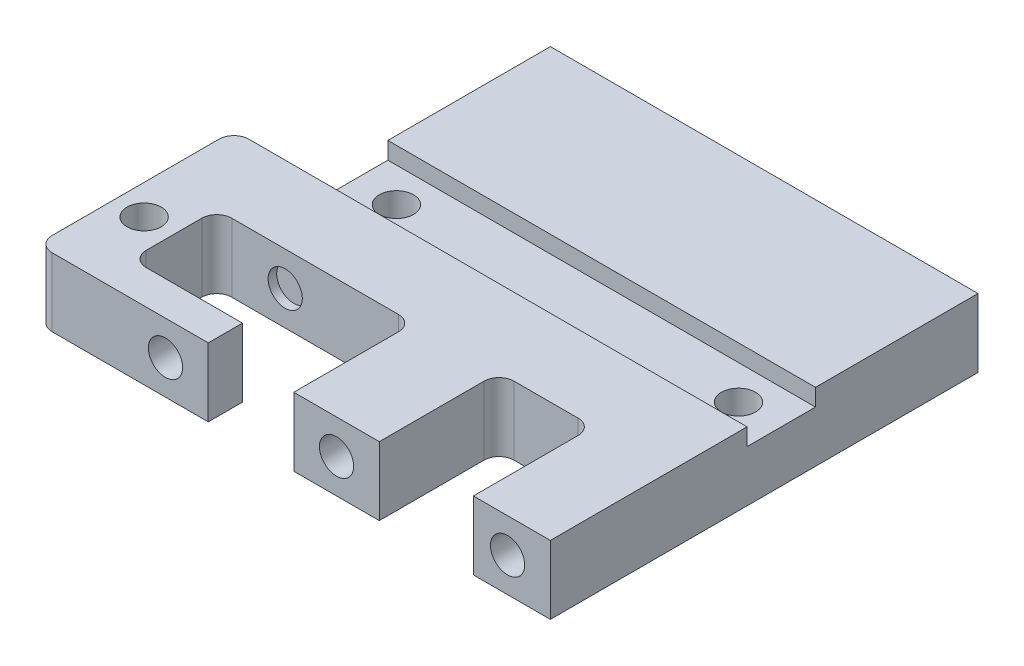
SolidWorks part; units mm, degrees
material "PVC rigide"
ref_plane "Plan de face" through (0, 0, 0) normal (0, 0, 1) x (1, 0, 0)
ref_plane "Plan de dessus" through (0, 0, 0) normal (0, 1, 0) x (1, 0, 0)
ref_plane "Plan de droite" through (0, 0, 0) normal (1, 0, 0) x (0, 0, -1)
sketch "Esquisse1" plane through (0, 0, 0) normal (0, 1, 0) x (1, 0, 0)
  line L1 (-57.1481, 46.0417) -> (-7.1481, 46.0417)
  line L2 (-57.1481, 46.0417) -> (-57.1481, 10.0417)
  line L4 (-7.1481, 46.0417) -> (-7.1481, 16.0417)
  line L5 (-48.1481, 10.0417) -> (-37.1481, 10.0417)
  line L6 (-16.1481, 10.0417) -> (-16.1481, -3.9583)
  line L7 (-16.1481, -3.9583) -> (-7.1481, -3.9583)
  line L8 (-7.1481, -3.9583) -> (-7.1481, 16.0417)
  line L9 (-27.1481, 10.0417) -> (-16.1481, 10.0417)
  line L10 (-48.1481, 10.0417) -> (-57.1481, 10.0417)
  line L11 (-37.1481, 10.0417) -> (-37.1481, -3.9583)
  line L12 (-37.1481, -3.9583) -> (-27.1481, -3.9583)
  line L13 (-27.1481, 10.0417) -> (-27.1481, -3.9583)
  dimension "D4" = 20
  dimension "D1" = 50
  dimension "D2" = 14
  dimension "D3" = 50
  dimension "D5" = 9
  dimension "D6" = 20
extrude "Boss.-Extru.1" add sketch "Esquisse1" along normal blind 8
sketch "Esquisse3" plane through (0, 0, -46.0417) normal (0, 0, -1) x (-1, 0, 0)
  line L0 (7.1481, 4) -> (57.1481, 4) construction
  line L1 (7.1481, 8) -> (7.1481, 0) construction
  line L2 (57.1481, 8) -> (57.1481, 0) construction
  circle A0 centre (12.1481, 4) radius 2
  circle A1 centre (52.1481, 4) radius 2
  dimension "D1" = 4
  dimension "D2" = 5
  dimension "D3" = 5
extrude "Enlèv. mat.-Extru.2" cut sketch "Esquisse3" against normal blind 10
sketch "Esquisse4" plane through (0, 8, 0) normal (0, 1, 0) x (1, 0, 0)
  line L0 (-62.8741, 23.0417) -> (2.0024, 23.0417) construction
  line L1 (-7.1481, 46.0417) -> (-57.1481, 46.0417) construction
  line L2 (-57.1481, 46.0417) -> (-57.1481, 10.0417) construction
  line L3 (-7.1481, -3.9583) -> (-7.1481, 46.0417) construction
  circle A0 centre (-52.1481, 23.0417) radius 2
  circle A1 centre (-12.1481, 23.0417) radius 2
  dimension "D2" = 4
  dimension "D1" = 23
  dimension "D3" = 5
  dimension "D4" = 5
extrude "Enlèv. mat.-Extru.3" cut sketch "Esquisse4" against normal blind 10
chamfer "Chanfrein1" distance 2.5 angle 45 2 edges at (-52.1481, 0, -25.0417) (-12.1481, 0, -25.0417)
sketch "Esquisse5" plane through (0, 8, 0) normal (0, 1, 0) x (1, 0, 0)
  line L0 (-57.1481, 46.0417) -> (-57.1481, 10.0417) construction
  line L1 (-57.1481, 27.0417) -> (-7.1481, 27.0417)
  line L2 (-57.1481, 27.0417) -> (-57.1481, 19.0417)
  line L3 (-57.1481, 19.0417) -> (-7.1481, 19.0417)
  line L4 (-7.1481, 27.0417) -> (-7.1481, 19.0417)
  line L5 (-7.1481, -3.9583) -> (-7.1481, 46.0417) construction
  circle A0 centre (-52.1481, 23.0417) radius 2 construction
  dimension "D1" = 4
  dimension "D2" = 8
extrude "Enlèv. mat.-Extru.4" cut sketch "Esquisse5" against normal blind 2
sketch "Esquisse6" plane through (-57.1481, 0, 0) normal (-1, 0, 0) x (0, 0, 1)
  line L0 (-46.0417, 0) -> (-10.0417, 0) construction
  line L1 (-19.0417, 8) -> (3.9583, 8)
  line L2 (-19.0417, 8) -> (-19.0417, 0)
  line L3 (-19.0417, 0) -> (3.9583, 0)
  line L4 (3.9583, 8) -> (3.9583, 0)
  line L9 (3.9583, 8) -> (3.9583, 0) construction
extrude "Boss.-Extru.2" add sketch "Esquisse6" along normal blind 10
sketch "Esquisse7" plane through (-57.1481, 0, 0) normal (1, 0, 0) x (0, 0, -1)
  line L0 (10.0417, 0) -> (-3.9583, 0) construction
  line L1 (-3.9583, 8) -> (0.0417, 8)
  line L2 (-3.9583, 8) -> (-3.9583, 0)
  line L3 (-3.9583, 0) -> (0.0417, 0)
  line L4 (0.0417, 8) -> (0.0417, 0)
  dimension "D1" = 4
extrude "Boss.-Extru.3" add sketch "Esquisse7" along normal blind 10
sketch "Esquisse8" plane through (0, 8, 0) normal (0, 1, 0) x (1, 0, 0)
  line L0 (-60.1481, 8.2917) -> (-60.1481, 1.7917)
  line L1 (-57.1481, 10.0417) -> (-37.1481, 10.0417) construction
  line L2 (-47.1481, 0.0417) -> (-57.1481, 0.0417) construction
  line L3 (-67.1481, -3.9583) -> (-67.1481, 19.0417) construction
  line L4 (-58.3981, 10.0417) -> (-54.6427, 10.0417)
  line L5 (-54.6427, 10.0417) -> (-54.6427, 0.0417)
  line L6 (-54.6427, 0.0417) -> (-58.3981, 0.0417)
  arc A0 (-58.3981, 10.0417) -> (-60.1481, 8.2917) centre (-58.3981, 8.2917) ccw
  arc A1 (-60.1481, 1.7917) -> (-58.3981, 0.0417) centre (-58.3981, 1.7917) ccw
  point P11 (-60.1481, 5.0417)
  dimension "D1" = 3.5
  dimension "D2" = 7
extrude "Enlèv. mat.-Extru.5" cut sketch "Esquisse8" against normal up to next
sketch "Esquisse2" plane through (0, 0, 3.9583) normal (0, 0, 1) x (1, 0, 0)
  line L2 (-7.1481, 8) -> (-7.1481, 0) construction
  circle A0 centre (-52.1481, 4) radius 2
  circle A1 centre (-12.1481, 4) radius 2
  circle A2 centre (-32.1481, 4) radius 2
  point P15 (-12.1481, 4)
  dimension "D1" = 4
  dimension "D3" = 5
extrude "Enlèv. mat.-Extru.1" cut sketch "Esquisse2" against normal blind 15
fillet "Congé1" radius 1.75 6 edges at (-16.1481, 4, -10.0417) (-27.1481, 4, -10.0417) (-37.1481, 4, -10.0417) (-57.1481, 3, -19.0417) (-67.1481, 4, 3.9583) (-67.1481, 4, -19.0417)
sketch "Esquisse10" plane through (0, 8, 0) normal (0, 1, 0) x (1, 0, 0)
  line L0 (-60.1481, 5.0417) -> (-67.1481, 5.0417) construction
  line L1 (-60.1481, 8.2917) -> (-60.1481, 1.7917) construction
  line L2 (-67.1481, -2.2083) -> (-67.1481, 17.2917) construction
  circle A0 centre (-63.6481, 5.0417) radius 2
  dimension "D1" = 4
extrude "Enlèv. mat.-Extru.7" cut sketch "Esquisse10" against normal up to next
